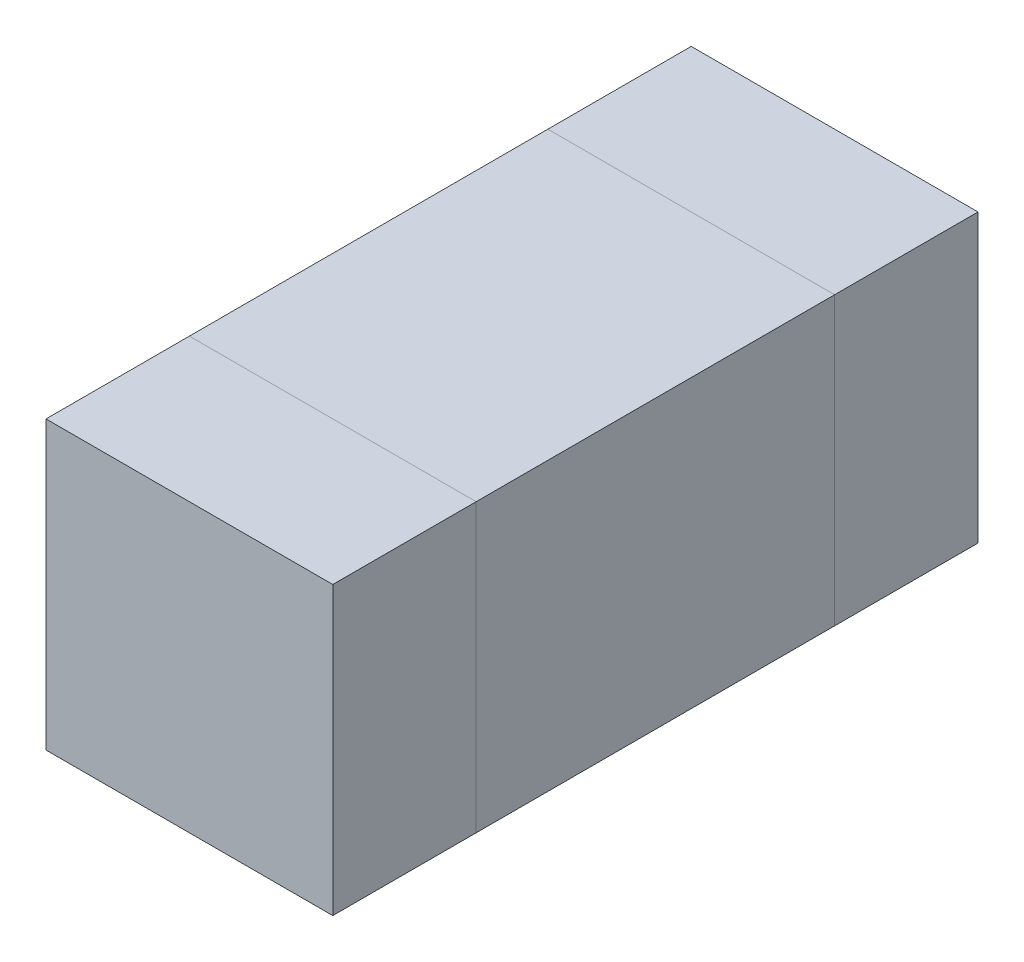
SolidWorks part; units mm, degrees
ref_plane "Front Plane" through (0, 0, 0) normal (0, 0, 1) x (1, 0, 0)
ref_plane "Top Plane" through (0, 0, 0) normal (0, 1, 0) x (1, 0, 0)
ref_plane "Right Plane" through (0, 0, 0) normal (1, 0, 0) x (0, 0, -1)
sketch "MainBodyS" plane through (0, 0, 0) normal (0, 1, 0) x (1, 0, 0)
  line L1 (-0.4, 0.5) -> (0.4, 0.5)
  line L2 (-0.4, 0.5) -> (-0.4, -0.5)
  line L3 (-0.4, -0.5) -> (0.4, -0.5)
  line L4 (0.4, 0.5) -> (0.4, -0.5)
  line L5 (-0.4, 0.5) -> (0.4, -0.5) construction
  line L6 (-0.4, -0.5) -> (0.4, 0.5) construction
  point P0 (0, 0)
  dimension "Length" = 1
  dimension "Width" = 0.8
extrude "MainBody" add sketch "MainBodyS" along normal blind 0.8
sketch "LeftBodyS" plane through (0, 0, 0) normal (0, -1, 0) x (-1, 0, 0)
  line L1 (0.4, -0.5) -> (-0.4, -0.5)
  line L2 (0.4, -0.5) -> (0.4, -0.9)
  line L3 (0.4, -0.9) -> (-0.4, -0.9)
  line L4 (-0.4, -0.5) -> (-0.4, -0.9)
  dimension "Width" = 0.4
extrude "Boss-Extrude1" add sketch "LeftBodyS" against normal up to surface (0.8 mm away) separate body up to face at (0, 0.8, 0)
sketch "RightBodyS" plane through (0, 0, 0) normal (0, -1, 0) x (1, 0, 0)
  line L0 (0.4, 0.5) -> (0.4, 0.9) construction
  line L1 (-0.4, -0.5) -> (0.4, -0.5)
  line L2 (-0.4, -0.5) -> (-0.4, -0.9)
  line L3 (-0.4, -0.9) -> (0.4, -0.9)
  line L4 (0.4, -0.5) -> (0.4, -0.9)
extrude "Boss-Extrude2" add sketch "RightBodyS" against normal up to surface (0.8 mm away) separate body up to face at (0, 0.8, 0)
